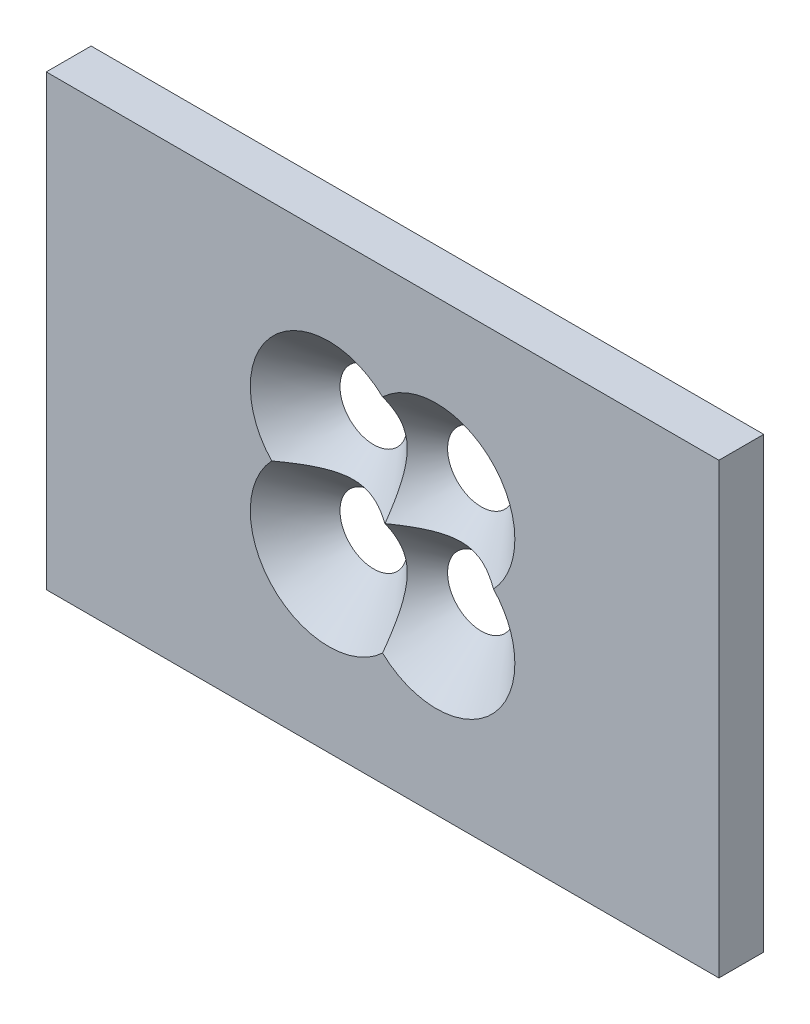
SolidWorks part; units mm, degrees
material "ABS"
ref_plane "Front Plane" through (0, 0, 0) normal (0, 0, 1) x (1, 0, 0)
ref_plane "Top Plane" through (0, 0, 0) normal (0, 1, 0) x (1, 0, 0)
ref_plane "Right Plane" through (0, 0, 0) normal (1, 0, 0) x (0, 0, -1)
sketch "Sketch1" plane through (0, 0, 0) normal (0, 0, 1) x (1, 0, 0)
  line L1 (-750, -500) -> (750, -500)
  line L2 (-750, -500) -> (-750, 500)
  line L3 (-750, 500) -> (750, 500)
  line L4 (750, -500) -> (750, 500)
  line L5 (-750, -500) -> (750, 500) construction
  line L6 (-750, 500) -> (750, -500) construction
  line L7 (-120, -120) -> (120, -120) construction
  line L8 (-120, -120) -> (-120, 120) construction
  line L9 (-120, 120) -> (120, 120) construction
  line L10 (120, -120) -> (120, 120) construction
  line L11 (-120, -120) -> (120, 120) construction
  line L12 (-120, 120) -> (120, -120) construction
  circle A0 centre (-120, 120) radius 75
  circle A1 centre (120, 120) radius 75
  circle A2 centre (120, -120) radius 75
  circle A3 centre (-120, -120) radius 75
  point P0 (0, 0)
  point P6 (0, 0)
  dimension "D5" = 150
  dimension "D6" = 150
  dimension "D7" = 150
  dimension "D8" = 150
  dimension "D1" = 1500
  dimension "D2" = 1000
  dimension "D3" = 240
  dimension "D4" = 240
extrude "Boss-Extrude1" add sketch "Sketch1" along normal blind 100
chamfer "Chamfer1" distance 100 angle 45 4 edges at (-45, -120, 100) (195, -120, 100) (195, 120, 100) (-45, 120, 100)
sketch3d "URDF Reference"
  line L0 (0, 0, 0) -> (10, 0, 0) construction
  line L1 (0, 0, 0) -> (0, 0, -10) construction
  point P0 (0, 0, 0)
  point P1 (0, 0, 0)
